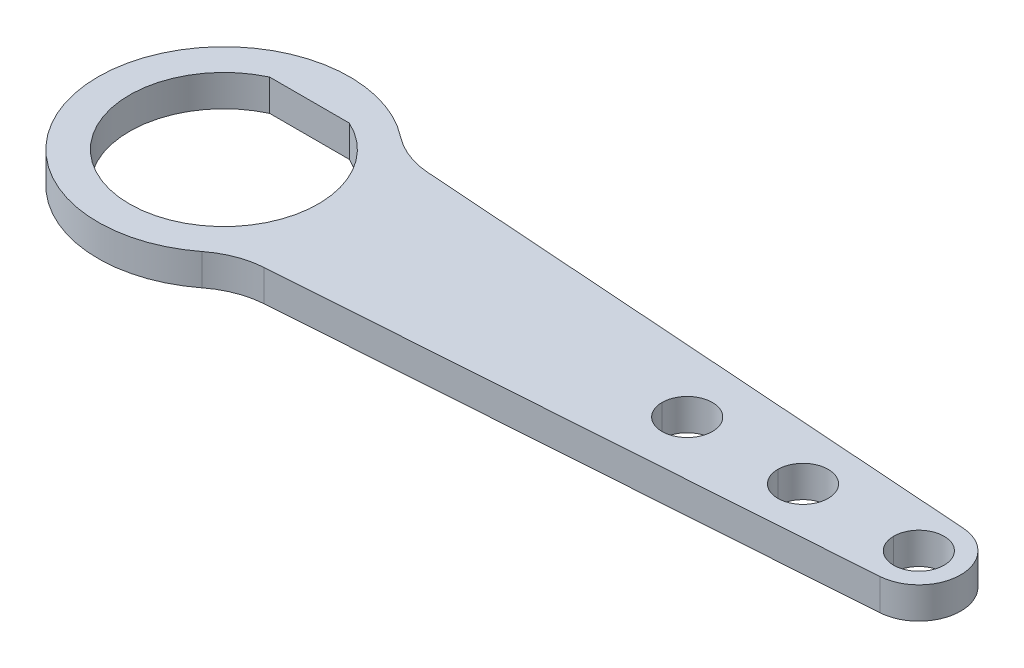
SolidWorks part; units mm, degrees
material "AISI 4130 Steel, annealed at 865C"
ref_plane "Front Plane" through (0, 0, 0) normal (0, 0, 1) x (1, 0, 0)
ref_plane "Top Plane" through (0, 0, 0) normal (0, 1, 0) x (1, 0, 0)
ref_plane "Right Plane" through (0, 0, 0) normal (1, 0, 0) x (0, 0, -1)
sketch "Sketch1" plane through (0, 0, 0) normal (0, 1, 0) x (1, 0, 0)
  line L3 (70.3988, 4.2087) -> (12.3315, 8.2754)
  line L4 (-55, 0) -> (55, 0) construction
  line L5 (70.3988, -4.2087) -> (12.3315, -8.2754)
  arc A2 (7.8186, -10.0079) -> (7.8186, 10.0079) centre (0, 0) cw
  arc A3 (70.3988, 4.2087) -> (70.3988, -4.2087) centre (70.104, 0) cw
  circle A4 centre (70.104, 0) radius 2.54
  circle A5 centre (58.42, 0) radius 2.54
  circle A6 centre (46.736, 0) radius 2.54
  arc A8 (12.3315, 8.2754) -> (7.8186, 10.0079) centre (12.9091, 16.5238) cw
  arc A9 (12.3315, -8.2754) -> (7.8186, -10.0079) centre (12.9091, -16.5238) ccw
  dimension "D1" = 5.08
  dimension "D3" = 12.7
  dimension "D4" = 5.08
  dimension "D5" = 46.736
  dimension "D2" = 58.42
  dimension "D6" = 70.104
sketch "Sketch3" plane through (0, 0, 0) normal (0, 1, 0) x (1, 0, 0)
  line L0 (-4.0181, 8.636) -> (4.0181, 8.636)
  arc A0 (4.0181, 8.636) -> (-4.0181, 8.636) centre (0, 0) cw
  point P3 (0, 8.636)
extrude "Boss-Extrude1" add sketch "Sketch1" along normal blind 3.175
extrude "Cut-Extrude1" cut sketch "Sketch3" against normal through all both and the other way through all
sketch "Sketch6" plane through (0, 0, 0) normal (0, -1, 0) x (1, 0, 0)
  line L0 (44.196, 0) -> (49.276, 0)
  line L1 (55.88, 0) -> (60.96, 0)
  line L2 (67.564, 0) -> (72.644, 0)
  circle A0 centre (46.736, 0) radius 2.54 construction
  circle A1 centre (58.42, 0) radius 2.54 construction
  circle A2 centre (70.104, 0) radius 2.54 construction
split line "Split Line1"
